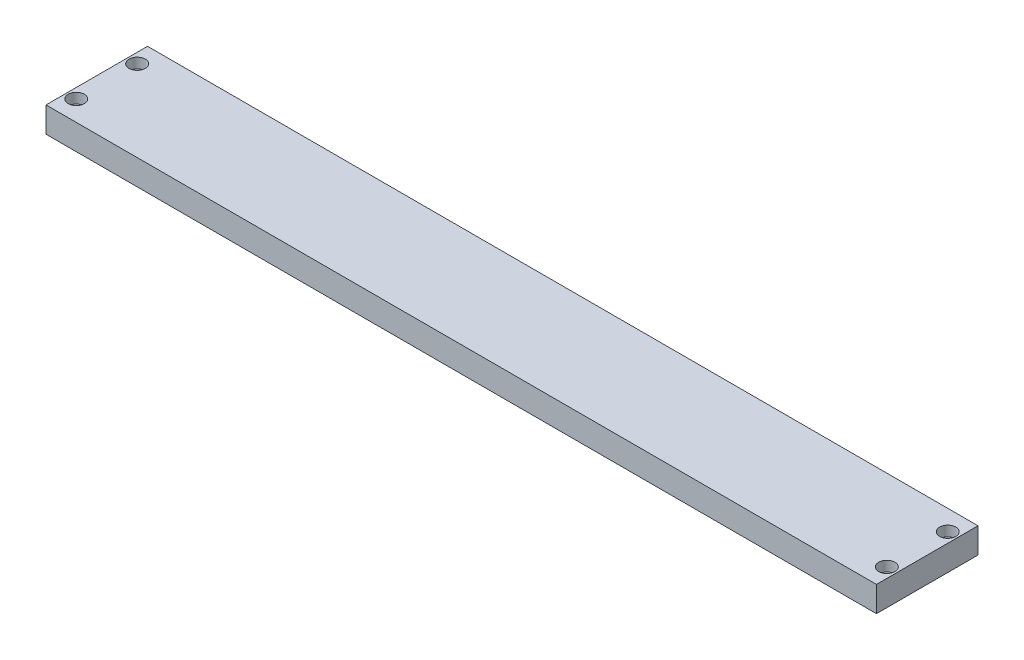
SolidWorks part; units mm, degrees
ref_plane "Front Plane" through (0, 0, 0) normal (0, 0, 1) x (1, 0, 0)
ref_plane "Top Plane" through (0, 0, 0) normal (0, 1, 0) x (1, 0, 0)
ref_plane "Right Plane" through (0, 0, 0) normal (1, 0, 0) x (0, 0, -1)
sketch "Sketch1" plane through (0, 0, 0) normal (0, 1, 0) x (1, 0, 0)
  line L1 (-81.785, -10) -> (81.785, -10)
  line L2 (-81.785, -10) -> (-81.785, 10)
  line L3 (-81.785, 10) -> (81.785, 10)
  line L4 (81.785, -10) -> (81.785, 10)
  line L5 (-81.785, -10) -> (81.785, 10) construction
  line L6 (-81.785, 10) -> (81.785, -10) construction
  circle A0 centre (-79.825, 6) radius 1
  circle A1 centre (-79.825, -6) radius 1
  circle A2 centre (79.825, 6) radius 1
  circle A3 centre (79.825, -6) radius 1
  point P0 (0, 0)
  dimension "D3" = 12
  dimension "D6" = 12
  dimension "D1" = 20
  dimension "D2" = 163.57
  dimension "D4" = 4
  dimension "D5" = 1.96
  dimension "D7" = 4
  dimension "D8" = 1.96
extrude "Boss-Extrude1" add sketch "Sketch1" along normal blind 5
sketch "Sketch2" plane through (0, 5, 0) normal (0, 1, 0) x (1, 0, 0)
  circle A0 centre (-79.825, 6) radius 1.6
  circle A1 centre (-79.825, -6) radius 1.6
  circle A2 centre (79.825, 6) radius 1.6
  circle A3 centre (79.825, -6) radius 1.6
extrude "Cut-Extrude1" cut sketch "Sketch2" against normal blind 2
